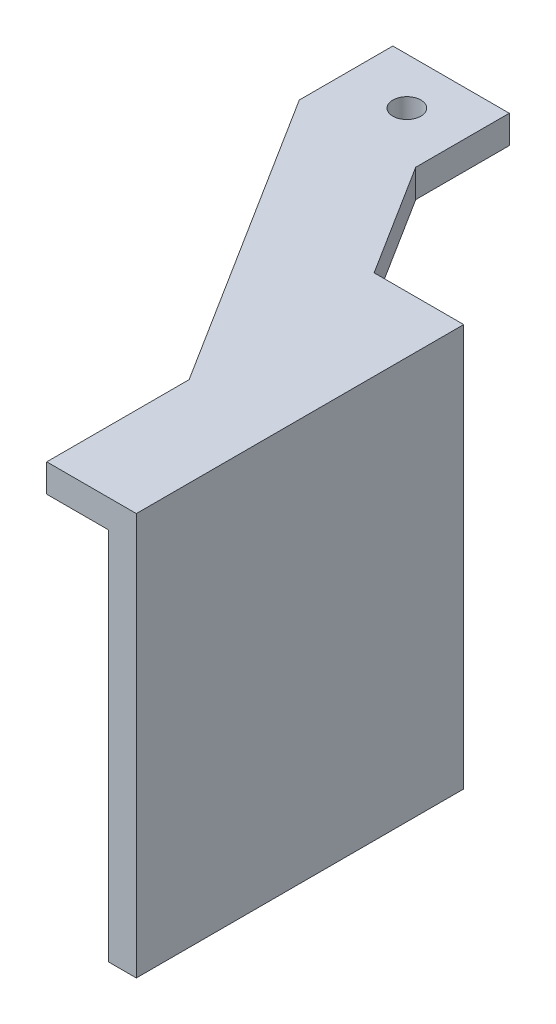
SolidWorks part; units mm, degrees
material "Perspex (TM) GS Acrylic Cast Sheet"
ref_plane "Front Plane" through (0, 0, 0) normal (0, 0, 1) x (1, 0, 0)
ref_plane "Top Plane" through (0, 0, 0) normal (0, 1, 0) x (1, 0, 0)
ref_plane "Right Plane" through (0, 0, 0) normal (1, 0, 0) x (0, 0, -1)
sketch "Sketch1" plane through (0, 0, 0) normal (0, 1, 0) x (1, 0, 0)
  line L0 (10, -5) -> (10, -52)
  line L1 (10, -5) -> (-10, -5)
  line L3 (10, 5) -> (-10, 5)
  line L4 (-10, -5) -> (-10, 5)
  line L5 (10, -5) -> (-10, 5) construction
  line L6 (10, 5) -> (-10, -5) construction
  line L7 (10, -52) -> (19.5785, -52)
  line L8 (19.5785, -52) -> (19.5785, 5)
  line L9 (19.5785, 5) -> (10, 5)
  point P0 (0, 0)
  dimension "D1" = 10
  dimension "D2" = 10
  dimension "D3" = 19.5785
  dimension "D4" = 52
extrude "Boss-Extrude1" add sketch "Sketch1" along normal blind 3
sketch "Sketch3" plane through (0, 0, 0) normal (0, -1, 0) x (1, 0, 0)
  line L0 (19.5785, 52) -> (19.5785, -5) construction
  line L1 (19.5785, 17) -> (16.5785, 17)
  line L2 (19.5785, 17) -> (19.5785, 52)
  line L3 (19.5785, 52) -> (16.5785, 52)
  line L4 (16.5785, 17) -> (16.5785, 52)
  line L5 (19.5785, 17) -> (16.5785, 52) construction
  line L6 (19.5785, 52) -> (16.5785, 17) construction
  line L7 (10, 52) -> (19.5785, 52) construction
  point P0 (18.0785, 34.5)
  dimension "D1" = 35
  dimension "D2" = 3
  dimension "D3" = 0
  dimension "5" = 0
extrude "Boss-Extrude2" add sketch "Sketch3" along normal blind 40
sketch "Sketch4" plane through (0, 0, 0) normal (0, 1, 0) x (1, 0, 0)
  line L0 (-10, 5) -> (-10, -5)
  line L1 (-10, -5) -> (19.5785, -52)
  line L2 (19.5785, -52) -> (19.5785, -17)
  line L3 (19.5785, -17) -> (10, -17)
  line L4 (10, -5) -> (10, -52) construction
  line L5 (-10, 5) -> (2.448, 5)
  line L6 (19.5785, 5) -> (-10, 5) construction
  line L10 (2.448, 5) -> (2.448, -5)
  line L11 (-10, -5) -> (10, -5) construction
  line L12 (2.448, -5) -> (10, -17)
extrude "Boss-Extrude3" add sketch "Sketch4" along normal blind 3
sketch "Sketch2" plane through (0, 3, 0) normal (0, 1, 0) x (1, 0, 0)
  line L0 (2.448, -5) -> (10, -5) construction
  line L1 (-10, 5) -> (-10, -5) construction
  circle A0 centre (-3.5, 0) radius 1.5
  dimension "D1" = 3
  dimension "D2" = 5
  dimension "D3" = 6.5
extrude "Cut-Extrude1" cut sketch "Sketch2" against normal blind 3
sketch "Sketch5" plane through (0, 0, 0) normal (0, 1, 0) x (1, 0, 0)
  line L3 (19.5785, 5) -> (-10, 5) construction
  line L4 (2.448, 5) -> (19.5785, 5)
  line L5 (19.5785, 5) -> (19.5785, -17)
  line L7 (2.448, -5) -> (2.448, 5)
  line L8 (19.5785, -17) -> (10, -17)
  line L9 (10, -17) -> (2.448, -5)
  line L10 (10, -17) -> (2.448, -5) construction
  point P1 (10, -17)
extrude "Cut-Extrude3" cut sketch "Sketch5" against normal mid plane 13
